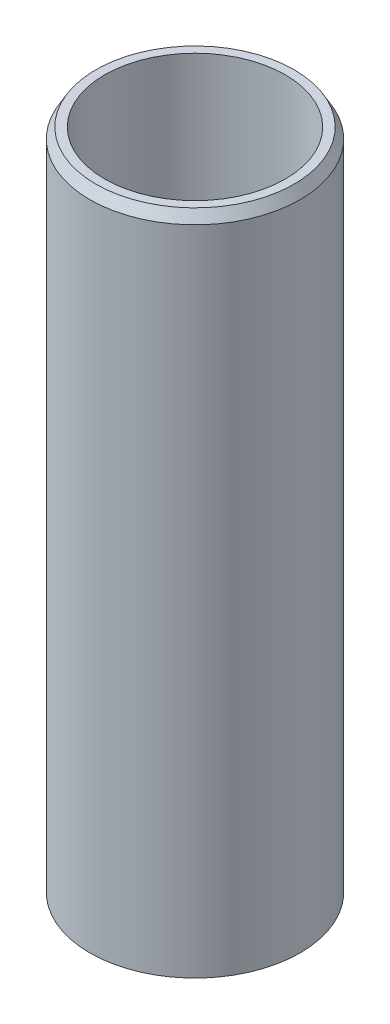
SolidWorks part; units mm, degrees
ref_plane "Front Plane" through (0, 0, 0) normal (0, 0, 1) x (1, 0, 0)
ref_plane "Top Plane" through (0, 0, 0) normal (0, 1, 0) x (1, 0, 0)
ref_plane "Right Plane" through (0, 0, 0) normal (1, 0, 0) x (0, 0, -1)
sketch "Sketch1" plane through (0, 0, 0) normal (0, 1, 0) x (1, 0, 0)
  circle A0 centre (0, 0) radius 57.5
  dimension "SHAFT_OD" = 115
extrude "Boss-Extrude1" add sketch "Sketch1" along normal blind 365.6518
sketch "Sketch2" plane through (0, 0, 0) normal (0, 1, 0) x (1, 0, 0)
  circle A0 centre (0, 0) radius 49.3757
  dimension "BORE_D" = 98.7515
extrude "Cut-Extrude1" cut sketch "Sketch2" along normal through all
chamfer "Chamfer1" distance 5.7057 angle 30 2 edges at (0, 365.6518, 57.5) (0, 0, 57.5) first distance on face at (0, 365.6518, 57.5) first distance on face at (0, 0, 49.3757)
